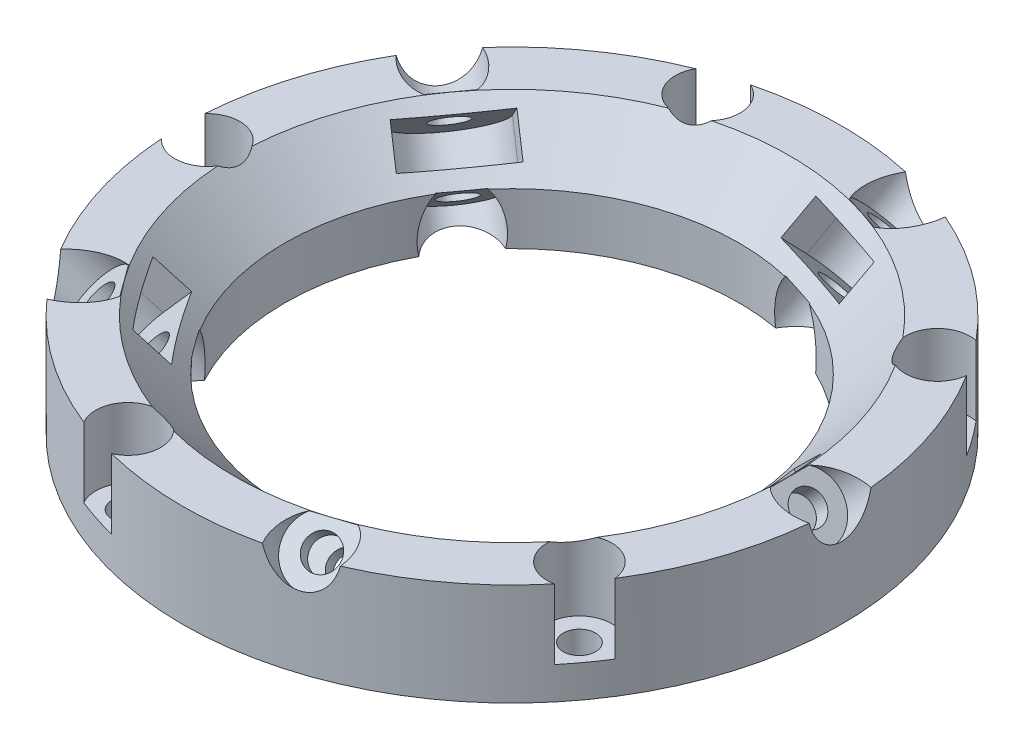
SolidWorks part; units mm, degrees
ref_plane "Front Plane" through (0, 0, 0) normal (0, 0, 1) x (1, 0, 0)
ref_plane "Top Plane" through (0, 0, 0) normal (0, 1, 0) x (1, 0, 0)
ref_plane "Right Plane" through (0, 0, 0) normal (1, 0, 0) x (0, 0, -1)
ref_axis "Axis1" through (0, 55, 0) along (0, -1, 0)
sketch "Sketch2" plane through (0, 0, 0) normal (0, 0, 1) x (1, 0, 0)
  line L0 (35.0503, 6.997) -> (35.0503, 14.997)
  line L1 (35.0503, 14.997) -> (42.8284, 22.7752)
  line L2 (42.8284, 22.7752) -> (50.8284, 22.7752)
  line L3 (50.8284, 22.7752) -> (50.8284, 6.997)
  line L4 (50.8284, 6.997) -> (35.0503, 6.997)
  line L5 (37.1716, 17.1184) -> (44.9497, 9.3402) construction
  line L6 (44.9497, 9.3402) -> (48.4853, 12.8757) construction
  line L7 (48.4853, 12.8757) -> (40.7071, 20.6539) construction
  line L8 (40, 14.2899) -> (43.5355, 17.8255) construction
  line L10 (0, 55) -> (0, -55) construction
  point P11 (0, 0)
  point P12 (0, 0)
  point P13 (0, 0)
  point P14 (0, 0)
  point P15 (68.1648, 19.7072)
  dimension "D1" = 11
  dimension "D2" = 5
  dimension "D3" = 7
  dimension "D4" = 3
  dimension "D5" = 45
  dimension "D6" = 3
  dimension "D7" = 8
  dimension "D8" = 8
  dimension "D9" = 40
ref_plane "Plane1" through (30.6805, 30.6805, 0) normal (0.7071, 0.7071, 0) x (0.7071, -0.7071, 0)
sketch "Sketch3" plane through (30.6805, 30.6805, 0) normal (0.7071, 0.7071, 0) x (0.7071, -0.7071, 0)
  line L0 (18.1798, -7) -> (11.1798, -7)
  line L2 (11.1798, 7) -> (18.1798, 7)
  line L3 (11.1798, 7) -> (11.1798, -7)
  circle A1 centre (18.1798, 0) radius 2.5
  arc A2 (18.1798, 7) -> (18.1798, -7) centre (18.1798, 0) cw
  point P0 (18.1798, 0)
  point P4 (0, 0)
  dimension "D1" = 5
revolve "Revolve1" add sketch "Sketch2" angle 360 about axis through (0, 55, 0) along (0, -1, 0)
extrude "Cut-Extrude1" cut sketch "Sketch3" against normal blind 5.5 and the other way blind 0.5
extrude "Cut-Extrude2" cut sketch "Sketch3<2>" against normal through all both and the other way through all contours A1
sketch "Sketch3<2>" plane through (30.6805, 30.6805, 0) normal (0.7071, 0.7071, 0) x (0.7071, -0.7071, 0) same geometry as "Sketch3"
sketch "Sketch5" plane through (26.7914, 26.7914, 0) normal (0.7071, 0.7071, 0) x (0, 0, -1)
  circle A0 centre (0, -18.1798) radius 5
  dimension "D1" = 10
extrude "Cut-Extrude3" cut sketch "Sketch5" against normal blind 8 from offset 2.5 offset against normal yes
extrude "Cut-Extrude4" cut sketch "Sketch5<2>" along normal blind 8 from offset 8.5
sketch "Sketch5<2>" plane through (26.7914, 26.7914, 0) normal (0.7071, 0.7071, 0) x (0, 0, -1) same geometry as "Sketch5"
pattern_circular "CirPattern1" count 5 over 360 about axis through (0, 55, 0) along (0, -1, 0) of "Cut-Extrude4", "Cut-Extrude3", "Cut-Extrude2", "Cut-Extrude1"
sketch "Sketch6" plane through (0, 0, 0) normal (0, 1, 0) x (1, 0, 0)
  circle A0 centre (-47, 0) radius 2.5
  dimension "D1" = 5
  dimension "D2" = 47
extrude "Cut-Extrude5" cut sketch "Sketch6" along normal blind 30.2
sketch "Sketch7" plane through (0, 0, 0) normal (0, 1, 0) x (1, 0, 0)
  circle A0 centre (-47, 0) radius 5
  dimension "D1" = 10
extrude "Cut-Extrude6" cut sketch "Sketch7" along normal through all from offset 12
pattern_circular "CirPattern2" count 5 over 360 about axis through (0, 55, 0) along (0, -1, 0) of "Cut-Extrude6", "Cut-Extrude5"
